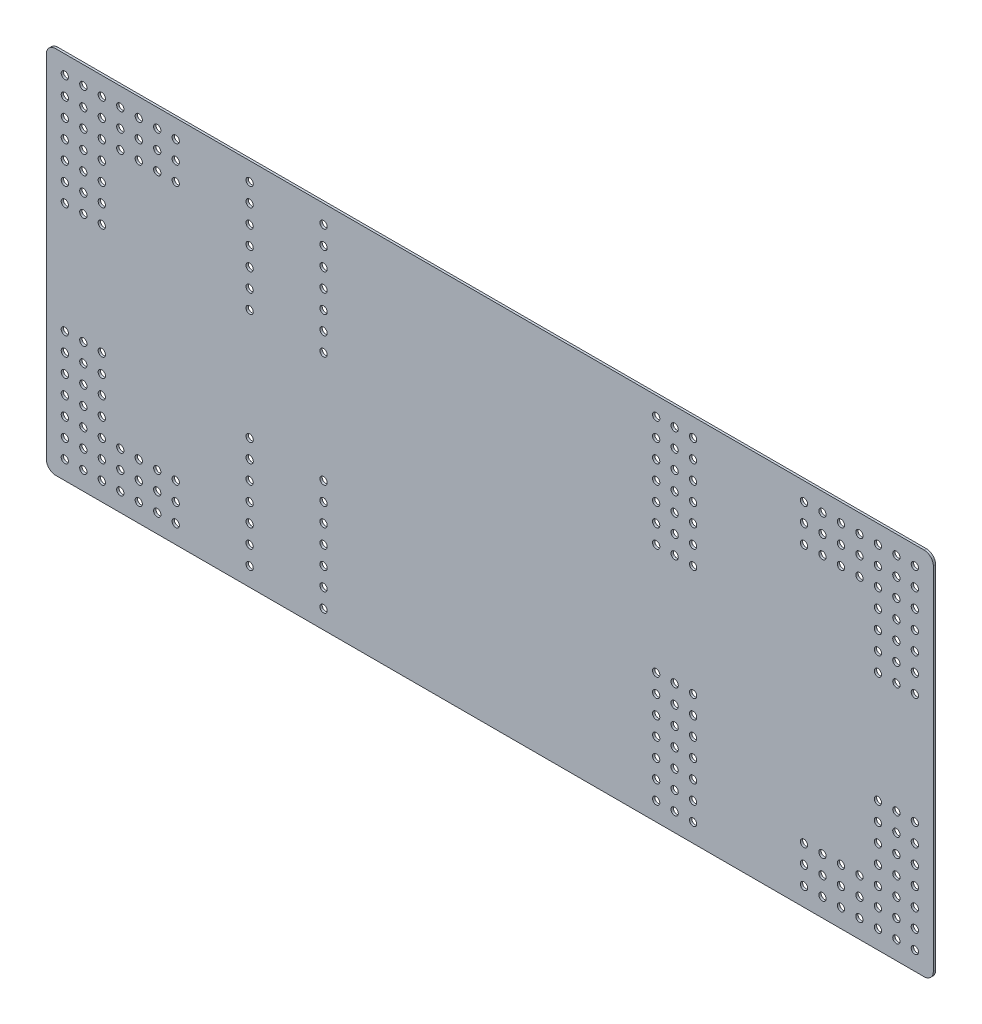
SolidWorks part; units mm, degrees
ref_plane "Front Plane" through (0, 0, 0) normal (0, 0, 1) x (1, 0, 0)
ref_plane "Top Plane" through (0, 0, 0) normal (0, 1, 0) x (1, 0, 0)
ref_plane "Right Plane" through (0, 0, 0) normal (1, 0, 0) x (0, 0, -1)
sketch "Sketch1" plane through (0, 0, 0) normal (0, 0, 1) x (1, 0, 0)
  line L1 (-148.9657, 122.234) -> (447.9343, 122.234)
  line L2 (-155.3157, 115.884) -> (-155.3157, -125.416)
  line L3 (-148.9657, -131.766) -> (447.9343, -131.766)
  line L4 (454.2843, 115.884) -> (454.2843, -125.416)
  arc A0 (-155.3157, -125.416) -> (-148.9657, -131.766) centre (-148.9657, -125.416) ccw
  arc A1 (447.9343, -131.766) -> (454.2843, -125.416) centre (447.9343, -125.416) ccw
  arc A2 (447.9343, 122.234) -> (454.2843, 115.884) centre (447.9343, 115.884) cw
  arc A3 (-148.9657, 122.234) -> (-155.3157, 115.884) centre (-148.9657, 115.884) ccw
  point P6 (-155.3157, -131.766)
  point P11 (454.2843, 122.234)
  point P14 (-155.3157, 122.234)
  dimension "D3" = 6.35
  dimension "D1" = 254
  dimension "D2" = 609.6
extrude "Boss-Extrude1" add sketch "Sketch1" along normal blind 1.5875
sketch "Sketch2" plane through (0, 0, 1.5875) normal (0, 0, 1) x (1, 0, 0)
  line L0 (447.9343, 122.234) -> (-148.9657, 122.234) construction
  line L1 (-155.3157, 115.884) -> (-155.3157, -125.416) construction
  line L2 (-155.3157, -4.766) -> (454.2843, -4.766) construction
  line L3 (454.2843, -125.416) -> (454.2843, 115.884) construction
  line L4 (149.4843, 122.234) -> (149.4843, -131.766) construction
  line L5 (-148.9657, -131.766) -> (447.9343, -131.766) construction
  circle A0 centre (-142.6157, 109.534) radius 2.5
  circle A1 centre (-129.9157, 109.534) radius 2.5
  circle A2 centre (-117.2157, 109.534) radius 2.5
  circle A3 centre (-104.5157, 109.534) radius 2.5
  circle A4 centre (-91.8157, 109.534) radius 2.5
  circle A5 centre (-79.1157, 109.534) radius 2.5
  circle A6 centre (-66.4157, 109.534) radius 2.5
  circle A7 centre (-129.9157, 96.834) radius 2.5
  circle A8 centre (-117.2157, 96.834) radius 2.5
  circle A9 centre (-104.5157, 96.834) radius 2.5
  circle A10 centre (-91.8157, 96.834) radius 2.5
  circle A11 centre (-79.1157, 96.834) radius 2.5
  circle A12 centre (-66.4157, 96.834) radius 2.5
  circle A13 centre (-129.9157, 84.134) radius 2.5
  circle A14 centre (-117.2157, 84.134) radius 2.5
  circle A15 centre (-104.5157, 84.134) radius 2.5
  circle A16 centre (-91.8157, 84.134) radius 2.5
  circle A17 centre (-79.1157, 84.134) radius 2.5
  circle A18 centre (-66.4157, 84.134) radius 2.5
  circle A19 centre (-142.6157, 96.834) radius 2.5
  circle A20 centre (-142.6157, 84.134) radius 2.5
  circle A24 centre (-142.6157, 71.434) radius 2.5
  circle A25 centre (-129.9157, 71.434) radius 2.5
  circle A26 centre (-117.2157, 71.434) radius 2.5
  circle A27 centre (-129.9157, 58.734) radius 2.5
  circle A28 centre (-117.2157, 58.734) radius 2.5
  circle A29 centre (-129.9157, 46.034) radius 2.5
  circle A30 centre (-117.2157, 46.034) radius 2.5
  circle A31 centre (-129.9157, 33.334) radius 2.5
  circle A32 centre (-117.2157, 33.334) radius 2.5
  circle A35 centre (-142.6157, 58.734) radius 2.5
  circle A36 centre (-142.6157, 46.034) radius 2.5
  circle A37 centre (-142.6157, 33.334) radius 2.5
  circle A39 centre (-142.6157, -42.866) radius 2.5
  circle A40 centre (-142.6157, -55.566) radius 2.5
  circle A41 centre (-142.6157, -68.266) radius 2.5
  circle A42 centre (-117.2157, -42.866) radius 2.5
  circle A43 centre (-129.9157, -42.866) radius 2.5
  circle A44 centre (-117.2157, -55.566) radius 2.5
  circle A45 centre (-129.9157, -55.566) radius 2.5
  circle A46 centre (-117.2157, -68.266) radius 2.5
  circle A47 centre (-129.9157, -68.266) radius 2.5
  circle A48 centre (-117.2157, -80.966) radius 2.5
  circle A49 centre (-129.9157, -80.966) radius 2.5
  circle A50 centre (-142.6157, -80.966) radius 2.5
  circle A51 centre (-142.6157, -93.666) radius 2.5
  circle A52 centre (-142.6157, -106.366) radius 2.5
  circle A53 centre (-66.4157, -93.666) radius 2.5
  circle A54 centre (-79.1157, -93.666) radius 2.5
  circle A55 centre (-91.8157, -93.666) radius 2.5
  circle A56 centre (-104.5157, -93.666) radius 2.5
  circle A57 centre (-117.2157, -93.666) radius 2.5
  circle A58 centre (-129.9157, -93.666) radius 2.5
  circle A59 centre (-66.4157, -106.366) radius 2.5
  circle A60 centre (-79.1157, -106.366) radius 2.5
  circle A61 centre (-91.8157, -106.366) radius 2.5
  circle A62 centre (-104.5157, -106.366) radius 2.5
  circle A63 centre (-117.2157, -106.366) radius 2.5
  circle A64 centre (-129.9157, -106.366) radius 2.5
  circle A65 centre (-66.4157, -119.066) radius 2.5
  circle A66 centre (-79.1157, -119.066) radius 2.5
  circle A67 centre (-91.8157, -119.066) radius 2.5
  circle A68 centre (-104.5157, -119.066) radius 2.5
  circle A69 centre (-117.2157, -119.066) radius 2.5
  circle A70 centre (-129.9157, -119.066) radius 2.5
  circle A71 centre (-142.6157, -119.066) radius 2.5
  circle A72 centre (441.5843, -119.066) radius 2.5
  circle A73 centre (428.8843, -119.066) radius 2.5
  circle A74 centre (416.1843, -119.066) radius 2.5
  circle A75 centre (403.4843, -119.066) radius 2.5
  circle A76 centre (390.7843, -119.066) radius 2.5
  circle A77 centre (378.0843, -119.066) radius 2.5
  circle A78 centre (365.3843, -119.066) radius 2.5
  circle A79 centre (428.8843, -106.366) radius 2.5
  circle A80 centre (416.1843, -106.366) radius 2.5
  circle A81 centre (403.4843, -106.366) radius 2.5
  circle A82 centre (390.7843, -106.366) radius 2.5
  circle A83 centre (378.0843, -106.366) radius 2.5
  circle A84 centre (365.3843, -106.366) radius 2.5
  circle A85 centre (428.8843, -93.666) radius 2.5
  circle A86 centre (416.1843, -93.666) radius 2.5
  circle A87 centre (403.4843, -93.666) radius 2.5
  circle A88 centre (390.7843, -93.666) radius 2.5
  circle A89 centre (378.0843, -93.666) radius 2.5
  circle A90 centre (365.3843, -93.666) radius 2.5
  circle A91 centre (441.5843, -106.366) radius 2.5
  circle A92 centre (441.5843, -93.666) radius 2.5
  circle A93 centre (441.5843, -80.966) radius 2.5
  circle A94 centre (428.8843, -80.966) radius 2.5
  circle A95 centre (416.1843, -80.966) radius 2.5
  circle A96 centre (428.8843, -68.266) radius 2.5
  circle A97 centre (416.1843, -68.266) radius 2.5
  circle A98 centre (428.8843, -55.566) radius 2.5
  circle A99 centre (416.1843, -55.566) radius 2.5
  circle A100 centre (428.8843, -42.866) radius 2.5
  circle A101 centre (416.1843, -42.866) radius 2.5
  circle A102 centre (441.5843, -68.266) radius 2.5
  circle A103 centre (441.5843, -55.566) radius 2.5
  circle A104 centre (441.5843, -42.866) radius 2.5
  circle A105 centre (441.5843, 33.334) radius 2.5
  circle A106 centre (441.5843, 46.034) radius 2.5
  circle A107 centre (441.5843, 58.734) radius 2.5
  circle A108 centre (416.1843, 33.334) radius 2.5
  circle A109 centre (428.8843, 33.334) radius 2.5
  circle A110 centre (416.1843, 46.034) radius 2.5
  circle A111 centre (428.8843, 46.034) radius 2.5
  circle A112 centre (416.1843, 58.734) radius 2.5
  circle A113 centre (428.8843, 58.734) radius 2.5
  circle A114 centre (416.1843, 71.434) radius 2.5
  circle A115 centre (428.8843, 71.434) radius 2.5
  circle A116 centre (441.5843, 71.434) radius 2.5
  circle A117 centre (441.5843, 84.134) radius 2.5
  circle A118 centre (441.5843, 96.834) radius 2.5
  circle A119 centre (365.3843, 84.134) radius 2.5
  circle A120 centre (378.0843, 84.134) radius 2.5
  circle A121 centre (390.7843, 84.134) radius 2.5
  circle A122 centre (403.4843, 84.134) radius 2.5
  circle A123 centre (416.1843, 84.134) radius 2.5
  circle A124 centre (428.8843, 84.134) radius 2.5
  circle A125 centre (365.3843, 96.834) radius 2.5
  circle A126 centre (378.0843, 96.834) radius 2.5
  circle A127 centre (390.7843, 96.834) radius 2.5
  circle A128 centre (403.4843, 96.834) radius 2.5
  circle A129 centre (416.1843, 96.834) radius 2.5
  circle A130 centre (428.8843, 96.834) radius 2.5
  circle A131 centre (365.3843, 109.534) radius 2.5
  circle A132 centre (378.0843, 109.534) radius 2.5
  circle A133 centre (390.7843, 109.534) radius 2.5
  circle A134 centre (403.4843, 109.534) radius 2.5
  circle A135 centre (416.1843, 109.534) radius 2.5
  circle A136 centre (428.8843, 109.534) radius 2.5
  circle A137 centre (441.5843, 109.534) radius 2.5
  circle A138 centre (-15.6157, 109.534) radius 2.5
  circle A139 centre (35.1843, 109.534) radius 2.5
  circle A140 centre (-15.6157, 96.834) radius 2.5
  circle A141 centre (35.1843, 96.834) radius 2.5
  circle A142 centre (-15.6157, 84.134) radius 2.5
  circle A143 centre (35.1843, 84.134) radius 2.5
  circle A144 centre (-15.6157, 71.434) radius 2.5
  circle A145 centre (35.1843, 71.434) radius 2.5
  circle A146 centre (-15.6157, 58.734) radius 2.5
  circle A147 centre (35.1843, 58.734) radius 2.5
  circle A148 centre (-15.6157, 46.034) radius 2.5
  circle A149 centre (35.1843, 46.034) radius 2.5
  circle A150 centre (-15.6157, 33.334) radius 2.5
  circle A151 centre (35.1843, 33.334) radius 2.5
  circle A152 centre (35.1843, -42.866) radius 2.5
  circle A153 centre (-15.6157, -42.866) radius 2.5
  circle A154 centre (35.1843, -55.566) radius 2.5
  circle A155 centre (-15.6157, -55.566) radius 2.5
  circle A156 centre (35.1843, -68.266) radius 2.5
  circle A157 centre (-15.6157, -68.266) radius 2.5
  circle A158 centre (35.1843, -80.966) radius 2.5
  circle A159 centre (-15.6157, -80.966) radius 2.5
  circle A160 centre (35.1843, -93.666) radius 2.5
  circle A161 centre (-15.6157, -93.666) radius 2.5
  circle A162 centre (35.1843, -106.366) radius 2.5
  circle A163 centre (-15.6157, -106.366) radius 2.5
  circle A164 centre (35.1843, -119.066) radius 2.5
  circle A165 centre (-15.6157, -119.066) radius 2.5
  circle A166 centre (289.1843, 109.534) radius 2.5
  circle A167 centre (276.4843, 109.534) radius 2.5
  circle A168 centre (263.7843, 109.534) radius 2.5
  circle A169 centre (276.4843, 96.834) radius 2.5
  circle A170 centre (263.7843, 96.834) radius 2.5
  circle A171 centre (276.4843, 84.134) radius 2.5
  circle A172 centre (263.7843, 84.134) radius 2.5
  circle A173 centre (276.4843, 71.434) radius 2.5
  circle A174 centre (263.7843, 71.434) radius 2.5
  circle A175 centre (276.4843, 58.734) radius 2.5
  circle A176 centre (263.7843, 58.734) radius 2.5
  circle A177 centre (276.4843, 46.034) radius 2.5
  circle A178 centre (263.7843, 46.034) radius 2.5
  circle A179 centre (276.4843, 33.334) radius 2.5
  circle A180 centre (263.7843, 33.334) radius 2.5
  circle A181 centre (289.1843, 96.834) radius 2.5
  circle A182 centre (289.1843, 84.134) radius 2.5
  circle A183 centre (289.1843, 71.434) radius 2.5
  circle A184 centre (289.1843, 58.734) radius 2.5
  circle A185 centre (289.1843, 46.034) radius 2.5
  circle A186 centre (289.1843, 33.334) radius 2.5
  circle A187 centre (289.1843, -42.866) radius 2.5
  circle A188 centre (289.1843, -55.566) radius 2.5
  circle A189 centre (289.1843, -68.266) radius 2.5
  circle A190 centre (289.1843, -80.966) radius 2.5
  circle A191 centre (289.1843, -93.666) radius 2.5
  circle A192 centre (289.1843, -106.366) radius 2.5
  circle A193 centre (263.7843, -42.866) radius 2.5
  circle A194 centre (276.4843, -42.866) radius 2.5
  circle A195 centre (263.7843, -55.566) radius 2.5
  circle A196 centre (276.4843, -55.566) radius 2.5
  circle A197 centre (263.7843, -68.266) radius 2.5
  circle A198 centre (276.4843, -68.266) radius 2.5
  circle A199 centre (263.7843, -80.966) radius 2.5
  circle A200 centre (276.4843, -80.966) radius 2.5
  circle A201 centre (263.7843, -93.666) radius 2.5
  circle A202 centre (276.4843, -93.666) radius 2.5
  circle A203 centre (263.7843, -106.366) radius 2.5
  circle A204 centre (276.4843, -106.366) radius 2.5
  circle A205 centre (263.7843, -119.066) radius 2.5
  circle A206 centre (276.4843, -119.066) radius 2.5
  circle A207 centre (289.1843, -119.066) radius 2.5
  dimension "D3" = 5
  dimension "D7" = 5
  dimension "D11" = 5
  dimension "D14" = 5
  dimension "D19" = 5
  dimension "D1" = 12.7
  dimension "D2" = 12.7
  dimension "D6" = 50.8
  dimension "D8" = 12.7
  dimension "D12" = 139.7
  dimension "D13" = 12.7
  dimension "D15" = 50.8
  dimension "D16" = 12.7
  dimension "D18" = 165.1
  dimension "D20" = 12.7
  dimension "D4" = 7
  dimension "D5" = 3
  dimension "D9" = 3
  dimension "D10" = 4
  dimension "D17" = 7
  dimension "D21" = 3
  dimension "D22" = 7
extrude "Cut-Extrude1" cut sketch "Sketch2" against normal through all
